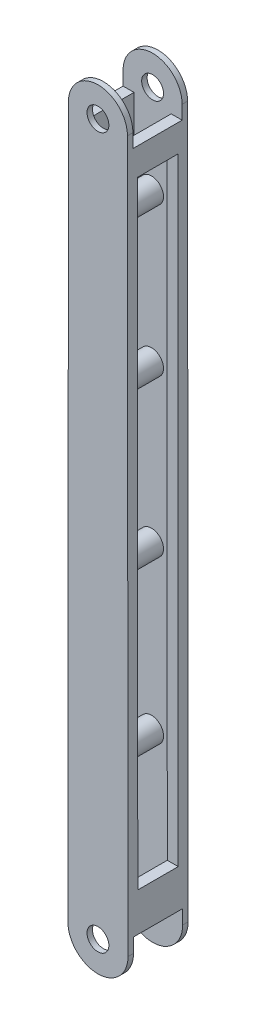
SolidWorks part; units mm, degrees
ref_plane "Front Plane" through (0, 0, 0) normal (0, 0, 1) x (1, 0, 0)
ref_plane "Top Plane" through (0, 0, 0) normal (0, 1, 0) x (1, 0, 0)
ref_plane "Right Plane" through (0, 0, 0) normal (1, 0, 0) x (0, 0, -1)
sketch "Sketch1" plane through (0, 0, 0) normal (0, 0, 1) x (1, 0, 0)
  line L0 (0, 0) -> (0, 650) construction
  line L1 (27, 650) -> (27.5, 0)
  line L2 (-27, 650) -> (-27.5, 0)
  line L3 (-27.49, 12.9767) -> (-17.49, 12.9767)
  line L4 (-17.49, 12.9767) -> (-17.0097, 637.4191)
  line L5 (-27.0097, 637.4191) -> (-17.0097, 637.4191)
  line L6 (-16.9839, 670.9893) -> (-16.6055, 1162.8403)
  line L7 (27.0097, 637.4191) -> (17.0097, 637.4191)
  line L8 (27.49, 12.9767) -> (17.49, 12.9767)
  line L9 (17.49, 12.9767) -> (17.0097, 637.4191)
  circle A0 centre (0, 0) radius 10
  arc A1 (-27.5, 0) -> (27.5, 0) centre (0, 0) ccw
  arc A2 (27, 650) -> (-27, 650) centre (0, 650) ccw
  circle A3 centre (0, 650) radius 10
  dimension "D1" = 20
  dimension "D2" = 55
  dimension "D4" = 20
  dimension "D5" = 54
  dimension "D3" = 650
  dimension "D6" = 10
extrude "Boss-Extrude2" add sketch "Sketch1" along normal blind 5 contours L1 A2 L2 L5 L4 L3 A1 L8 L9 L7 A0 A3 region at (0, 322.8762, 0)
extrude "Boss-Extrude3" add sketch "Sketch1<3>" along normal blind 55 contours L9 L8 L1 L7 | L5 L2 L3 L4 region at (22.2498, 325.1979, 0) region at (-22.2498, 325.1979, 0)
sketch "Sketch1<3>" plane through (0, 0, 0) normal (0, 0, 1) x (1, 0, 0) same geometry as "Sketch1"
extrude "Boss-Extrude4" add sketch "Sketch1<4>" along normal blind 5 from offset 50 contours L1 A2 L2 L5 L4 L3 A1 L8 L9 L7 A0 A3 region at (0, 322.8762, 0)
sketch "Sketch1<4>" plane through (0, 0, 0) normal (0, 0, 1) x (1, 0, 0) same geometry as "Sketch1"
sketch "Sketch3" plane through (27.5, 0.0212, 0) normal (1, 0.0008, 0) x (0, 0, -1)
  line L0 (-9, 612.558) -> (-9, 48.2414)
  line L1 (-50, 637.3981) -> (-5, 637.3981) construction
  line L2 (-27.5, 637.3981) -> (-27.5, 612.558) construction
  line L3 (-9, 612.558) -> (-46, 612.558)
  line L5 (-9, 48.2414) -> (-46, 48.2414)
  line L6 (-46, 612.558) -> (-46, 48.2414)
  line L7 (-27.5, 48.2414) -> (-27.5, 0) construction
  point P10 (0, 0)
  point P11 (0, 0)
  point P12 (0, 0)
extrude "Cut-Extrude1" cut sketch "Sketch3" against normal through all both and the other way through all
sketch "Sketch4" plane through (0, 0, 55) normal (0, 0, 1) x (1, 0, 0)
  line L0 (0, 677) -> (0, -27.5) construction
  arc A0 (27, 650) -> (-27, 650) centre (0, 650) ccw construction
  arc A1 (-27.5, 0) -> (27.5, 0) centre (0, 0) ccw construction
  circle A2 centre (0, 569.2555) radius 11
  circle A3 centre (0, 433.1613) radius 11
  circle A4 centre (0, 290.1663) radius 11
  circle A5 centre (0, 141.9388) radius 11
  point P16 (0, 141.9388)
  point P17 (0, 0)
  point P18 (0, 433.1613)
  point P19 (0, 569.2555)
  dimension "D1" = 22
extrude "Boss-Extrude5" add sketch "Sketch4" against normal blind 49
